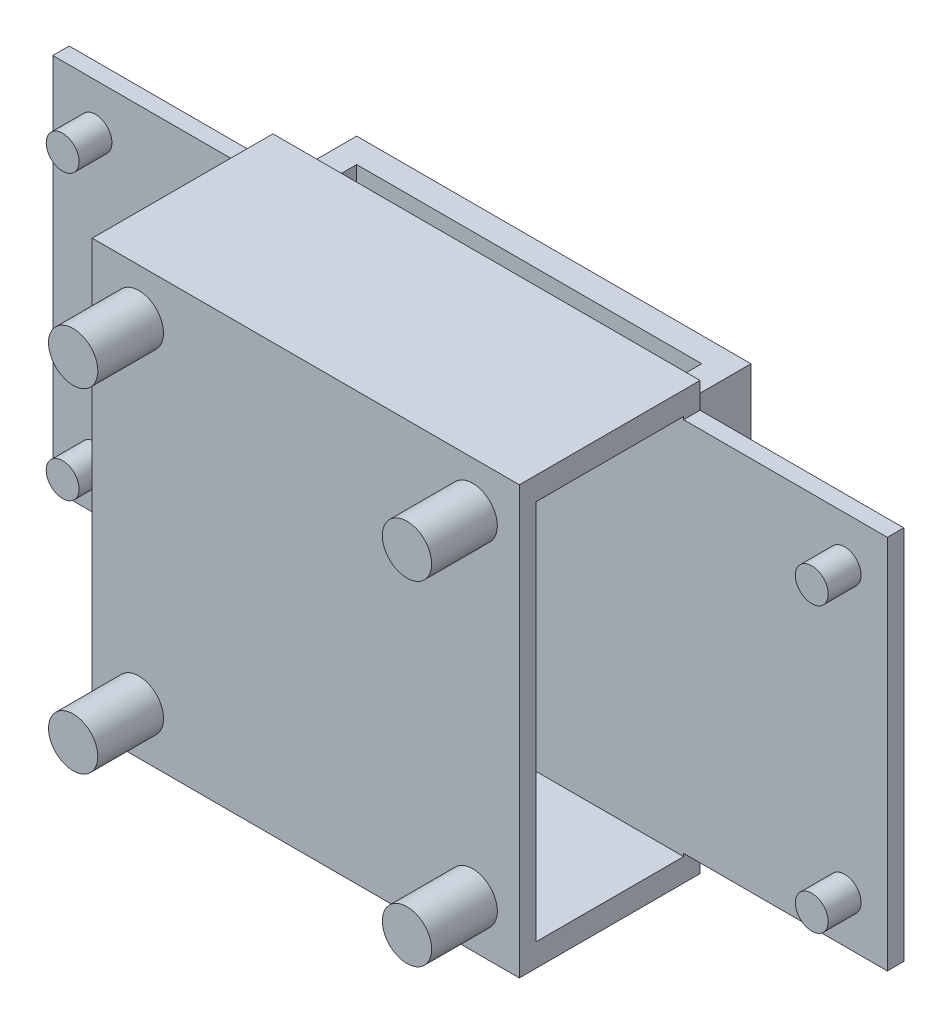
SolidWorks part; units mm, degrees
ref_plane "前视基准面" through (0, 0, 0) normal (0, 0, 1) x (1, 0, 0)
ref_plane "上视基准面" through (0, 0, 0) normal (0, 1, 0) x (1, 0, 0)
ref_plane "右视基准面" through (0, 0, 0) normal (1, 0, 0) x (0, 0, -1)
sketch "草图1" plane through (0, 0, 0) normal (0, 0, 1) x (1, 0, 0)
  line L0 (-13, -11.43) -> (-13, -13)
  line L1 (-25.4, 11.43) -> (-13, 11.43)
  line L2 (-25.4, 11.43) -> (-25.4, -11.43)
  line L3 (-25.4, -11.43) -> (-13, -11.43)
  line L4 (25.4, 11.43) -> (25.4, -11.43)
  line L5 (-25.4, 11.43) -> (25.4, -11.43) construction
  line L6 (-25.4, -11.43) -> (25.4, 11.43) construction
  line L7 (-13, 13) -> (13, 13)
  line L8 (-13, 13) -> (-13, 11.43)
  line L9 (-13, -13) -> (13, -13)
  line L10 (13, 13) -> (13, 11.43)
  line L11 (-13, 13) -> (13, -13) construction
  line L12 (-13, -13) -> (13, 13) construction
  line L13 (13, -11.43) -> (25.4, -11.43)
  line L14 (13, -11.43) -> (13, -13)
  line L15 (13, 11.43) -> (25.4, 11.43)
  point P0 (0, 0)
  point P6 (0, 0)
extrude "凸台-拉伸1" add sketch "草图1" along normal blind 1
sketch "草图3" plane through (0, 0, 1) normal (0, 0, 1) x (1, 0, 0)
  line L0 (-25.4, -11.43) -> (-22.8, -11.43) construction
  line L1 (-25.4, -11.43) -> (-13, -11.43) construction
  line L2 (-22.8, -11.43) -> (-22.8, -8.63) construction
  line L3 (0, 0) -> (-2, 0) construction
  line L4 (0, 0) -> (0, 2) construction
  circle A0 centre (-22.8, -8.63) radius 1
  circle A1 centre (-22.8, 8.63) radius 1
  circle A2 centre (22.8, -8.63) radius 1
  circle A3 centre (22.8, 8.63) radius 1
extrude "凸台-拉伸2" add sketch "草图3" along normal blind 2
sketch "草图6" plane through (0, 0, 0) normal (0, 0, -1) x (-1, 0, 0)
  line L0 (19.2, 11.43) -> (-12.1, 11.43) construction
  line L1 (13, 11.43) -> (25.4, 11.43) construction
  line L2 (19.2, 11.43) -> (10.5, 11.43) construction
  line L3 (0, 0) -> (4, 0) construction
  line L4 (-12.1, 11.43) -> (11.9, 11.43)
  line L5 (-12.1, 11.43) -> (-12.1, 7.43)
  line L6 (-12.1, 7.43) -> (11.9, 7.43)
  line L7 (11.9, 11.43) -> (11.9, 7.43)
  line L8 (-12.1, -7.43) -> (11.9, -7.43)
  line L9 (11.9, -11.43) -> (11.9, -7.43)
  line L10 (-12.1, -11.43) -> (11.9, -11.43)
  line L11 (-12.1, -11.43) -> (-12.1, -7.43)
sketch "草图9" plane through (0, 0, 1) normal (0, 0, 1) x (1, 0, 0)
  line L0 (0, 0) -> (3, 0) construction
  line L1 (-13, 13) -> (13, 13)
  line L2 (-13, 13) -> (-13, 11.6)
  line L3 (-13, 11.6) -> (13, 11.6)
  line L4 (13, 13) -> (13, 11.6)
  line L5 (-13, -11.6) -> (13, -11.6)
  line L6 (13, -13) -> (13, -11.6)
  line L7 (-13, -13) -> (13, -13)
  line L8 (-13, -13) -> (-13, -11.6)
extrude "凸台-拉伸4" add sketch "草图9" along normal blind 9
sketch "草图10" plane through (0, 0, 10) normal (0, 0, 1) x (1, 0, 0)
  line L1 (-13, 13) -> (13, 13)
  line L2 (-13, 13) -> (-13, -13)
  line L3 (-13, -13) -> (13, -13)
  line L4 (13, 13) -> (13, -13)
extrude "凸台-拉伸5" add sketch "草图10" along normal blind 1
sketch "草图11" plane through (0, 0, 11) normal (0, 0, 1) x (1, 0, 0)
  line L0 (-12.7, -12.7) -> (-10.16, -12.7) construction
  line L1 (-12.7, 12.7) -> (12.7, 12.7) construction
  line L2 (-12.7, 12.7) -> (-12.7, -12.7) construction
  line L3 (-12.7, -12.7) -> (12.7, -12.7) construction
  line L4 (12.7, 12.7) -> (12.7, -12.7) construction
  line L5 (-12.7, 12.7) -> (12.7, -12.7) construction
  line L6 (-12.7, -12.7) -> (12.7, 12.7) construction
  line L7 (-10.16, -12.7) -> (-10.16, -10.16) construction
  line L8 (0, 0) -> (4, 0) construction
  line L9 (0, 0) -> (0, 4) construction
  circle A0 centre (-10.16, -10.16) radius 1.5
  circle A1 centre (10.16, -10.16) radius 1.5
  circle A2 centre (10.16, 10.16) radius 1.5
  circle A3 centre (-10.16, 10.16) radius 1.5
  point P0 (0, 0)
extrude "凸台-拉伸6" add sketch "草图11" along normal blind 4
extrude "凸台-拉伸7" add sketch "草图6" along normal blind 4
sketch "草图12" plane through (0, -11.43, 0) normal (0, -1, 0) x (-1, 0, 0)
  line L0 (11.9, 4) -> (10.4, 4) construction
  line L1 (-12.1, 4) -> (11.9, 4) construction
  line L2 (10.4, 4) -> (10.4, 2.5) construction
  line L4 (10.4, 2.5) -> (-10.6, 2.5)
  line L5 (10.4, 2.5) -> (10.4, 0.5)
  line L6 (10.4, 0.5) -> (-10.6, 0.5)
  line L7 (-10.6, 2.5) -> (-10.6, 0.5)
  point P9 (0, 0)
extrude "切除-拉伸3" cut sketch "草图12" against normal blind 25
